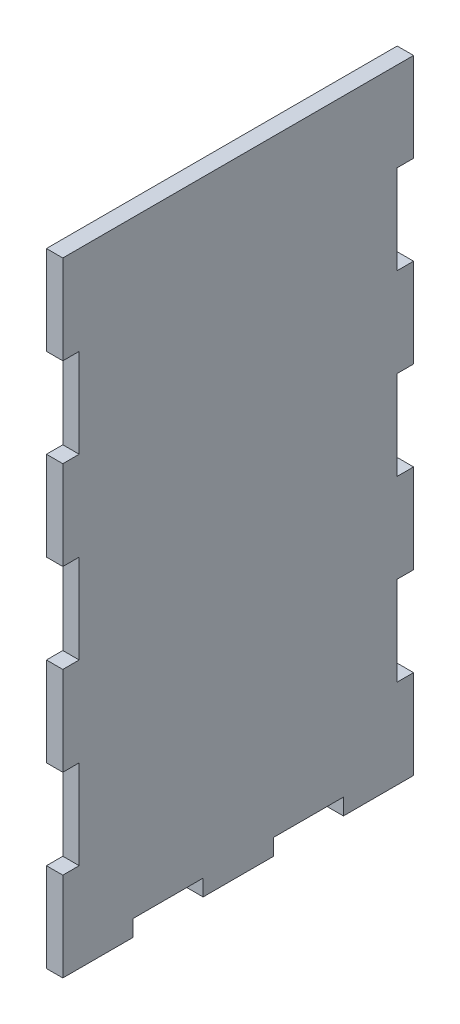
SolidWorks part; units mm, degrees
ref_plane "Front Plane" through (0, 0, 0) normal (0, 0, 1) x (1, 0, 0)
ref_plane "Top Plane" through (0, 0, 0) normal (0, 1, 0) x (1, 0, 0)
ref_plane "Right Plane" through (0, 0, 0) normal (1, 0, 0) x (0, 0, -1)
sketch "Sketch1" plane through (0, 0, 0) normal (1, 0, 0) x (0, 0, -1)
  line L1 (-57.15, -101.6) -> (57.15, -101.6)
  line L2 (-57.15, -101.6) -> (-57.15, 101.6)
  line L3 (-57.15, 101.6) -> (57.15, 101.6)
  line L4 (57.15, -101.6) -> (57.15, 101.6)
  line L5 (-57.15, -101.6) -> (57.15, 101.6) construction
  line L6 (-57.15, 101.6) -> (57.15, -101.6) construction
  point P0 (0, 0)
  dimension "D1" = 114.3
  dimension "D2" = 203.2
extrude "Boss-Extrude1" add sketch "Sketch1" along normal blind 5.334
sketch "Sketch3" plane through (5.334, 0, 0) normal (1, 0, 0) x (0, 0, -1)
  line L0 (-57.15, 101.6) -> (-57.15, -101.6) construction
  line L2 (-57.15, -72.5714) -> (-51.816, -72.5714)
  line L3 (-57.15, -72.5714) -> (-57.15, -43.5429)
  line L4 (-57.15, -43.5429) -> (-51.816, -43.5429)
  line L5 (-51.816, -72.5714) -> (-51.816, -43.5429)
  line L7 (-51.816, 72.5714) -> (-51.816, 101.6) construction
  line L8 (-57.15, -14.5143) -> (-51.816, -14.5143)
  line L9 (-57.15, -14.5143) -> (-57.15, 14.5143)
  line L10 (-57.15, 14.5143) -> (-51.816, 14.5143)
  line L11 (-51.816, -14.5143) -> (-51.816, 14.5143)
  line L12 (-57.15, 43.5429) -> (-51.816, 43.5429)
  line L13 (-57.15, 43.5429) -> (-57.15, 72.5714)
  line L14 (-57.15, 72.5714) -> (-51.816, 72.5714)
  line L15 (-51.816, 43.5429) -> (-51.816, 72.5714)
  line L16 (57.15, 101.6) -> (-57.15, 101.6) construction
  line L17 (-51.816, 43.5429) -> (-51.816, 14.5143) construction
  line L18 (-51.816, -14.5143) -> (-51.816, -43.5429) construction
  line L19 (-51.816, -72.5714) -> (-51.816, -101.6) construction
  line L20 (-57.15, -101.6) -> (57.15, -101.6) construction
  line L21 (0, 0) -> (0, 101.6) construction
  line L22 (51.816, -72.5714) -> (51.816, -101.6) construction
  line L23 (51.816, -14.5143) -> (51.816, -43.5429) construction
  line L24 (51.816, 43.5429) -> (51.816, 14.5143) construction
  line L25 (51.816, 72.5714) -> (51.816, 101.6) construction
  line L26 (51.816, 43.5429) -> (51.816, 72.5714)
  line L28 (57.15, 72.5714) -> (51.816, 72.5714)
  line L29 (57.15, 43.5429) -> (57.15, 72.5714)
  line L30 (57.15, 43.5429) -> (51.816, 43.5429)
  line L32 (51.816, -14.5143) -> (51.816, 14.5143)
  line L33 (57.15, 14.5143) -> (51.816, 14.5143)
  line L34 (57.15, -14.5143) -> (57.15, 14.5143)
  line L35 (57.15, -14.5143) -> (51.816, -14.5143)
  line L36 (51.816, -72.5714) -> (51.816, -43.5429)
  line L37 (57.15, -43.5429) -> (51.816, -43.5429)
  line L38 (57.15, -72.5714) -> (57.15, -43.5429)
  line L39 (57.15, -72.5714) -> (51.816, -72.5714)
  dimension "material" = 5.334
extrude "Cut-Extrude4" cut sketch "Sketch3" against normal through all
sketch "Sketch5" plane through (5.334, 0, 0) normal (1, 0, 0) x (0, 0, -1)
  line L0 (-57.15, -101.6) -> (57.15, -101.6) construction
  line L1 (-34.29, -101.6) -> (-11.43, -101.6)
  line L2 (-34.29, -101.6) -> (-34.29, -96.266)
  line L3 (-34.29, -96.266) -> (-11.43, -96.266)
  line L4 (-11.43, -101.6) -> (-11.43, -96.266)
  line L5 (-34.29, -96.266) -> (-57.15, -96.266) construction
  line L6 (11.43, -101.6) -> (34.29, -101.6)
  line L7 (11.43, -101.6) -> (11.43, -96.266)
  line L8 (11.43, -96.266) -> (34.29, -96.266)
  line L9 (34.29, -101.6) -> (34.29, -96.266)
  line L10 (-57.15, -72.5714) -> (-57.15, -101.6) construction
  line L11 (-11.43, -96.266) -> (11.43, -96.266) construction
  line L12 (34.29, -96.266) -> (57.15, -96.266) construction
  line L13 (57.15, -101.6) -> (57.15, -72.5714) construction
  dimension "material" = 5.334
extrude "Cut-Extrude5" cut sketch "Sketch5" against normal through all
equation "\"material\"=\"MDF@Platform.assembly\""
equation "\"D1@Boss-Extrude1\"=\"material\""
